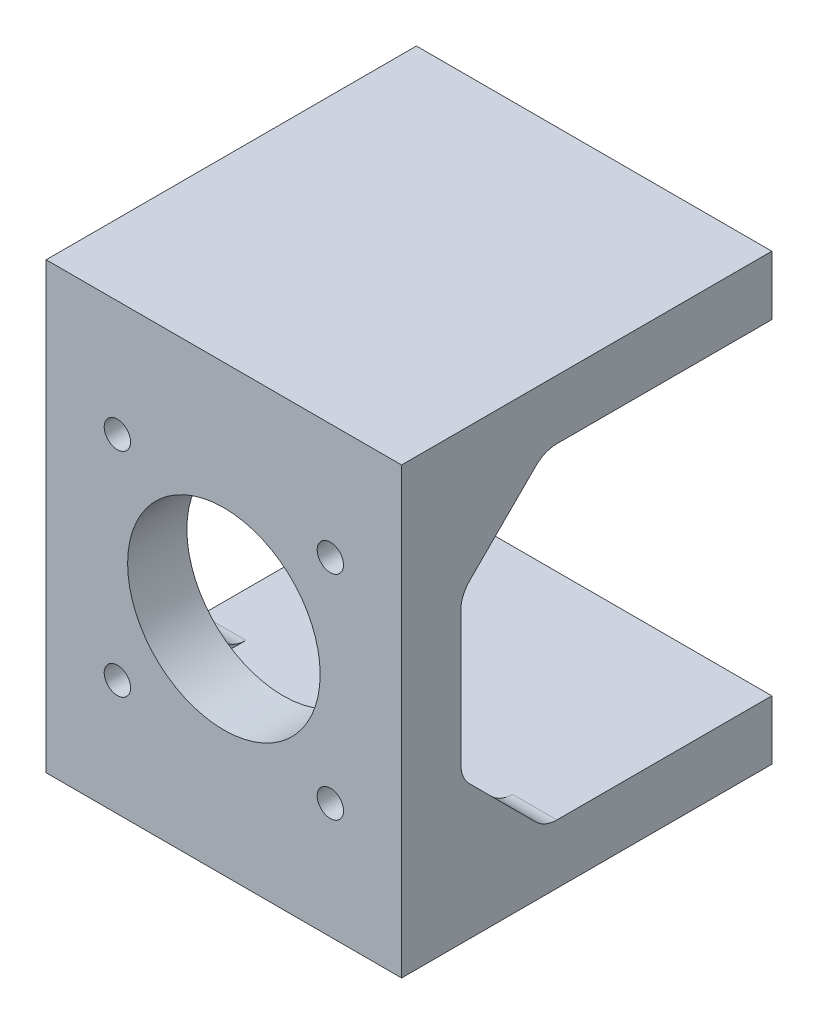
SolidWorks part; units mm, degrees
material "ABS"
ref_plane "Front Plane" through (0, 0, 0) normal (0, 0, 1) x (1, 0, 0)
ref_plane "Top Plane" through (0, 0, 0) normal (0, 1, 0) x (1, 0, 0)
ref_plane "Right Plane" through (0, 0, 0) normal (1, 0, 0) x (0, 0, -1)
sketch "Sketch1" plane through (0, 0, 0) normal (0, 0, 1) x (1, 0, 0)
  line L1 (-15.24, -19.05) -> (15.24, -19.05)
  line L2 (-15.24, -19.05) -> (-15.24, 19.05)
  line L3 (-15.24, 19.05) -> (15.24, 19.05)
  line L4 (15.24, -19.05) -> (15.24, 19.05)
  line L5 (-15.24, -19.05) -> (15.24, 19.05) construction
  line L6 (-15.24, 19.05) -> (15.24, -19.05) construction
  circle A0 centre (0, 0) radius 8.255
  point P0 (0, 0)
  dimension "D3" = 16.51
  dimension "D1" = 38.1
  dimension "D2" = 30.48
extrude "Boss-Extrude with 4-40 Tap Drill Holes" add sketch "Sketch1" against normal mid plane 31.75
hole_wizard "#4-40 Tapped Hole1" positions "Sketch7" profile "Sketch8" tap size "#4-40" standard "ANSI Inch" end condition up to next
sketch "Sketch7" plane through (0, 0, 15.875) normal (0, 0, 1) x (1, 0, 0)
  line L9 (-9.1313, 9.1313) -> (9.1313, 9.1313) construction
  line L10 (-9.1313, 9.1313) -> (-9.1313, -9.1313) construction
  line L11 (-9.1313, -9.1313) -> (9.1313, -9.1313) construction
  line L12 (9.1313, 9.1313) -> (9.1313, -9.1313) construction
  point P212 (-9.1313, 9.1313)
  point P213 (9.1313, -9.1313)
  point P216 (-9.1313, -9.1313)
  point P217 (9.1313, 9.1313)
  point P289 (9.1313, 0)
  point P293 (0, -9.1313)
  dimension "D1" = 18.2626
  dimension "D2" = 18.2626
sketch "Sketch8" plane through (-9.1313, 9.1313, 15.875) normal (1, 0, 0) x (0, -1, 0)
  line L0 (0, 0) -> (0, 31.75)
  line L1 (0, 31.75) -> (1.1303, 31.75)
  line L2 (1.1303, 31.75) -> (1.1303, 0)
  line L5 (1.1303, 0) -> (0, 0)
  line L11 (0, -6.35) -> (0, 107.95) construction
  dimension "Thru Tap Drill Dia." = 2.2606
  dimension "Thru Tap Drill Depth" = 31.75
cosmetic thread "Hole Thread1" parameters "D2"=2.8448
cosmetic thread "Hole Thread2" parameters "D2"=2.8448
cosmetic thread "Hole Thread3" parameters "D2"=2.8448
cosmetic thread "Hole Thread4" parameters "D2"=2.8448
sketch "Sketch3" plane through (15.24, 0, 0) normal (1, 0, 0) x (0, 0, -1)
  line L0 (15.875, -19.05) -> (15.875, 19.05) construction
  line L1 (15.875, 13.97) -> (-10.795, 13.97)
  line L2 (15.875, 13.97) -> (15.875, -13.97)
  line L3 (15.875, -13.97) -> (-10.795, -13.97)
  line L4 (-10.795, 13.97) -> (-10.795, -13.97)
  line L5 (15.875, 19.05) -> (-15.875, 19.05) construction
  line L6 (15.875, -19.05) -> (-15.875, -19.05) construction
  line L7 (-15.875, -19.05) -> (-15.875, 19.05) construction
  dimension "D1" = 5.08
  dimension "D2" = 5.08
  dimension "D3" = 5.08
extrude "Cut-Extrude1" cut sketch "Sketch3" against normal up to next
fillet "Fillet1" radius 2.54 2 edges at (0, -13.97, 10.795) (0, 13.97, 10.795)
sketch "Sketch5" plane through (0, 19.05, 0) normal (0, 1, 0) x (1, 0, 0)
  line L4 (-15.24, 15.875) -> (-15.24, -8.255)
  line L5 (-15.24, 15.875) -> (-15.24, -8.255)
  line L6 (15.24, -8.255) -> (15.24, 15.875)
  line L7 (15.24, 15.875) -> (-15.24, 15.875)
  line L8 (-15.24, -8.255) -> (15.24, -8.255)
  line L9 (-15.24, -8.255) -> (15.24, -8.255)
  line L10 (15.24, -8.255) -> (15.24, 15.875)
  line L11 (15.24, 15.875) -> (-15.24, 15.875)
  circle A0 centre (-6.35, 10.795) radius 1.65
  circle A1 centre (6.35, 10.795) radius 1.65
  circle A2 centre (6.35, -4.445) radius 1.65
  circle A3 centre (-6.35, -4.445) radius 1.65
  dimension "D2" = 3.3
  dimension "D3" = 8.89
  dimension "D4" = 8.89
  dimension "D5" = 5.08
  dimension "D1" = 0
extrude "Clearance Holes for M3 Screw" [suppressed] cut sketch "Sketch5" against normal through all contours A0 | A3 | A2 | A1
sketch "Sketch6" plane through (15.24, 0, 0) normal (1, 0, 0) x (0, 0, -1)
  line L0 (-10.795, -6.7858) -> (-3.6108, -13.97)
  line L1 (-10.795, 11.43) -> (-10.795, -11.43) construction
  line L2 (-8.255, -13.97) -> (15.875, -13.97) construction
  line L3 (0, 0) -> (-15.875, 0) construction
  line L4 (-15.875, -19.05) -> (-15.875, 19.05) construction
  line L6 (-8.255, 13.97) -> (-3.6108, 13.97)
  line L7 (-8.255, -13.97) -> (-3.6108, -13.97)
  line L8 (-10.795, -6.7858) -> (-10.795, -11.43)
  line L9 (-10.795, 6.7858) -> (-3.6108, 13.97)
  line L10 (-10.795, 6.7858) -> (-10.795, 11.43)
  arc A1 (-10.795, -11.43) -> (-8.255, -13.97) centre (-8.255, -11.43) ccw construction
  arc A2 (-10.795, 11.43) -> (-8.255, 13.97) centre (-8.255, 11.43) cw
  arc A3 (-10.795, -11.43) -> (-8.255, -13.97) centre (-8.255, -11.43) ccw
  point P11 (-10.795, -6.1787)
  dimension "D1" = 45
  dimension "D2" = 10.16
extrude "Boss-Extrude1" add sketch "Sketch6" against normal blind 3.81
mirror "Mirror1" about plane through (0, 0, 0) normal (1, 0, 0) of "Boss-Extrude1"
fillet "Fillet2" radius 2.54 8 edges at (-13.335, 13.97, 3.6108) (-13.335, 6.7858, 10.795) (-13.335, -13.97, 3.6108) (-13.335, -6.7858, 10.795) (13.335, -13.97, 3.6108) (13.335, -6.7858, 10.795) (13.335, 13.97, 3.6108) (13.335, 6.7858, 10.795)
